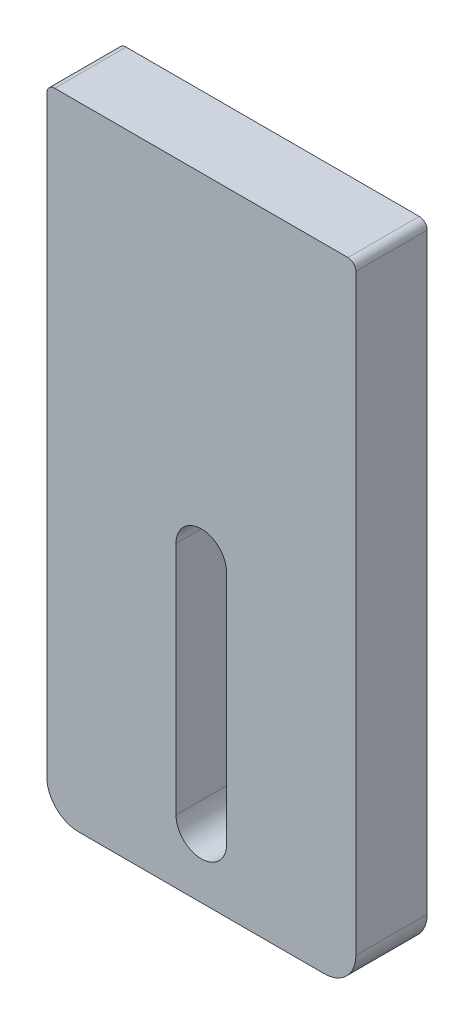
SolidWorks part; units mm, degrees
ref_plane "Front Plane" through (0, 0, 0) normal (0, 0, 1) x (1, 0, 0)
ref_plane "Top Plane" through (0, 0, 0) normal (0, 1, 0) x (1, 0, 0)
ref_plane "Right Plane" through (0, 0, 0) normal (1, 0, 0) x (0, 0, -1)
sketch "Sketch1" plane through (0, 0, 0) normal (0, 0, 1) x (1, 0, 0)
  line L0 (0, 0) -> (10, 0) construction
  line L1 (0, 0) -> (0, 10) construction
  line L2 (23.5124, -45.3134) -> (-19.7958, -27.0738) construction
  line L3 (-10, 21) -> (10, 21) construction
  line L4 (10, 21) -> (10, -39.6225) construction
  line L5 (-10, -31.1994) -> (-10, 21) construction
  line L6 (23.5124, -45.3134) -> (-19.7958, -27.0738) construction
  line L7 (-10, 21) -> (10, 21) construction
  line L8 (10, 21) -> (10, -39.6225) construction
  line L9 (-10, -31.1994) -> (-10, 21) construction
  line L11 (0, 72.5) -> (0, -10) construction
  line L12 (-1.6, -35.8818) -> (-1.6, -21.0509)
  line L13 (1.6, -21.0509) -> (1.6, -35.8818)
  line L14 (9.75, -39.8818) -> (9.75, 0)
  line L15 (9.75, 0) -> (-9.75, 0)
  line L16 (-9.75, 0) -> (-9.75, -39.8818)
  line L17 (-9.75, -39.8818) -> (9.75, -39.8818)
  line L18 (0, -34.8818) -> (0, -39.8818) construction
  line L19 (0, 0) -> (0, -10) construction
  line L20 (0, -35.8818) -> (0, -21.0509) construction
  line L21 (-10, -39.8818) -> (10, -39.8818) construction
  circle A0 centre (0, 0) radius 10 construction
  circle A1 centre (0, 0) radius 10 construction
  circle A2 centre (0, -35.8818) radius 4 construction
  circle A3 centre (14, -30.4565) radius 4 construction
  arc A4 (1.6, -21.0509) -> (-1.6, -21.0509) centre (0, -21.0509) ccw
  arc A5 (-1.6, -35.8818) -> (1.6, -35.8818) centre (0, -35.8818) ccw
  circle A6 centre (0, 72.5) radius 91.9509 construction
  circle A7 centre (0, 72.5) radius 91.9509 construction
  dimension "D4" = 1.6
  dimension "D1" = 0.5
  dimension "D2" = 5
  dimension "D3" = 10
extrude "Boss-Extrude1" add sketch "Sketch1" along normal blind 5
fillet "Fillet1" radius 2 2 edges at (-9.75, -39.8818, 2.5) (9.75, -39.8818, 2.5)
sketch "Sketch2" plane through (0, 0, 0) normal (0, 0, 1) x (1, 0, 0)
  line L0 (9.75, -39.8818) -> (9.75, 0) construction
  line L1 (9.75, 0) -> (-9.75, 0) construction
  line L2 (-9.75, 0) -> (-9.75, -39.8818) construction
  line L3 (9.75, -10) -> (9.75, 0)
  line L4 (9.75, 0) -> (-9.75, 0)
  line L5 (-9.75, 0) -> (-9.75, -10)
  line L6 (-9.75, -10) -> (9.75, -10)
  circle A0 centre (0, 0) radius 10 construction
extrude "Cut-Extrude1" cut sketch "Sketch2" along normal blind 0.5
fillet "Fillet2" radius 0.5 2 edges at (9.75, 0, 2.75) (-9.75, 0, 2.75)
chamfer "Chamfer1" distance 0.5 angle 45 5 edges at (-9.75, -23.9409, 0) (-9.1642, -39.296, 0) (0, -39.8818, 0) (9.1642, -39.296, 0) (9.75, -23.9409, 0)
